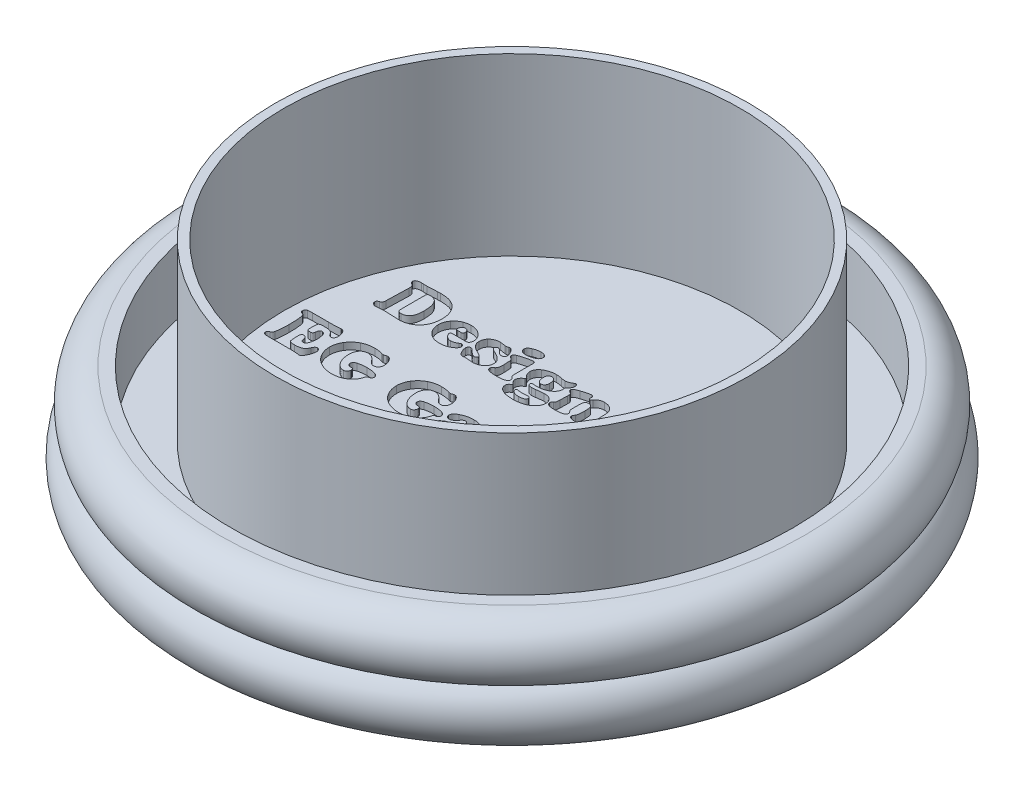
SolidWorks part; units mm, degrees
ref_plane "Front Plane" through (0, 0, 0) normal (0, 0, 1) x (1, 0, 0)
ref_plane "Top Plane" through (0, 0, 0) normal (0, 1, 0) x (1, 0, 0)
ref_plane "Right Plane" through (0, 0, 0) normal (1, 0, 0) x (0, 0, -1)
sketch "Sketch2" plane through (0, 0, 0) normal (0, 0, 1) x (1, 0, 0)
  line L0 (0, 0) -> (44.45, 0)
  line L2 (42.418, 15.875) -> (40.64, 15.875)
  line L3 (40.64, 15.875) -> (40.64, 6.35)
  line L4 (40.64, 6.35) -> (34.29, 6.35)
  line L5 (34.29, 6.35) -> (34.29, 31.75)
  line L6 (34.29, 31.75) -> (33.02, 31.75)
  line L7 (33.02, 31.75) -> (33.02, 6.35)
  line L8 (33.02, 6.35) -> (0, 6.35)
  line L9 (0, 6.35) -> (0, 0)
  arc A0 (45.8983, 8.2529) -> (42.418, 15.875) centre (42.1616, 11.1523) ccw
  arc A1 (45.8983, 8.2529) -> (44.45, 0) centre (43.0124, 4.5058) cw
  point P14 (44.7351, 7.1422)
  point P15 (0, 0)
  point P16 (0, 0)
  point P17 (33.02, 7.7099)
  point P18 (0, 0)
  point P19 (0, 0)
  point P20 (42.545, 6.35)
  point P21 (41.8629, 6.35)
  point P22 (0, 0)
  point P23 (0, 0)
  point P24 (0, 0)
  point P25 (41.9078, 6.35)
  point P26 (43.1451, 6.35)
  point P27 (43.4534, 6.35)
  point P28 (0, 0)
  point P29 (42.545, 12.7)
  point P30 (42.545, 12.7407)
  point P31 (42.545, 12.7254)
  point P32 (42.418, 0)
  point P33 (42.418, 12.5627)
  point P34 (0, 0)
  point P35 (44.45, 7.6863)
  point P36 (45.6253, 8.2723)
  point P37 (45.8983, 8.2529)
  dimension "D1" = 44.45
  dimension "D2" = 6.35
  dimension "D3" = 34.29
  dimension "D4" = 9.525
  dimension "D5" = 25.4
  dimension "D6" = 33.02
  dimension "D7" = 1.778
  dimension "D8" = 6.35
revolve "Revolve1" add sketch "Sketch2" angle 360 about L9
sketch "Sketch3" plane through (0, 6.35, 0) normal (0, 1, 0) x (1, 0, 0)
  line L0 (-32.1864, 7.2352) -> (33.02, 7.2352) construction
  text T0 "Designed by\r\nEG Gabbai 24'\r\n2026" font "Cooper Black" height 6.35
  point P6 (0, 0)
  point P7 (0, 0)
extrude "Cut-Extrude4" cut sketch "Sketch3" against normal blind 1
